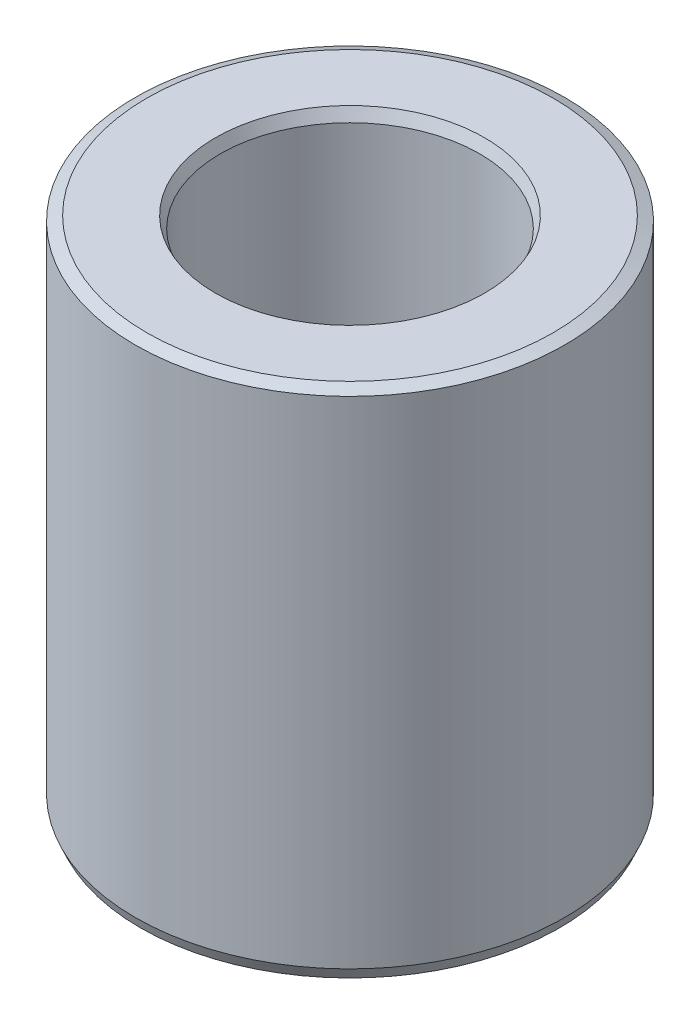
SolidWorks part; units mm, degrees
ref_plane "Front Plane" through (0, 0, 0) normal (0, 0, 1) x (1, 0, 0)
ref_plane "Top Plane" through (0, 0, 0) normal (0, 1, 0) x (1, 0, 0)
ref_plane "Right Plane" through (0, 0, 0) normal (1, 0, 0) x (0, 0, -1)
sketch "Sketch1" plane through (0, 0, 0) normal (0, 1, 0) x (1, 0, 0)
  circle A0 centre (0, 0) radius 15
  dimension "SLEEVE_OD" = 30
extrude "Boss-Extrude1" add sketch "Sketch1" along normal blind 35.7987
sketch "Sketch2" plane through (0, 0, 0) normal (0, 1, 0) x (1, 0, 0)
  circle A0 centre (0, 0) radius 9.0624
  dimension "BORE_D" = 18.1247
extrude "Cut-Extrude1" cut sketch "Sketch2" along normal through all
chamfer "Chamfer1" distance 0.3486 angle 66.351 4 edges at (0, 35.7987, 9.0624) (0, 0, 9.0624) (0, 0, 15) (0, 35.7987, 15) first distance on face at (0, 35.7987, 9.0624) first distance on face at (0, 0, 9.0624) first distance on face at (0, 35.7987, 15)
